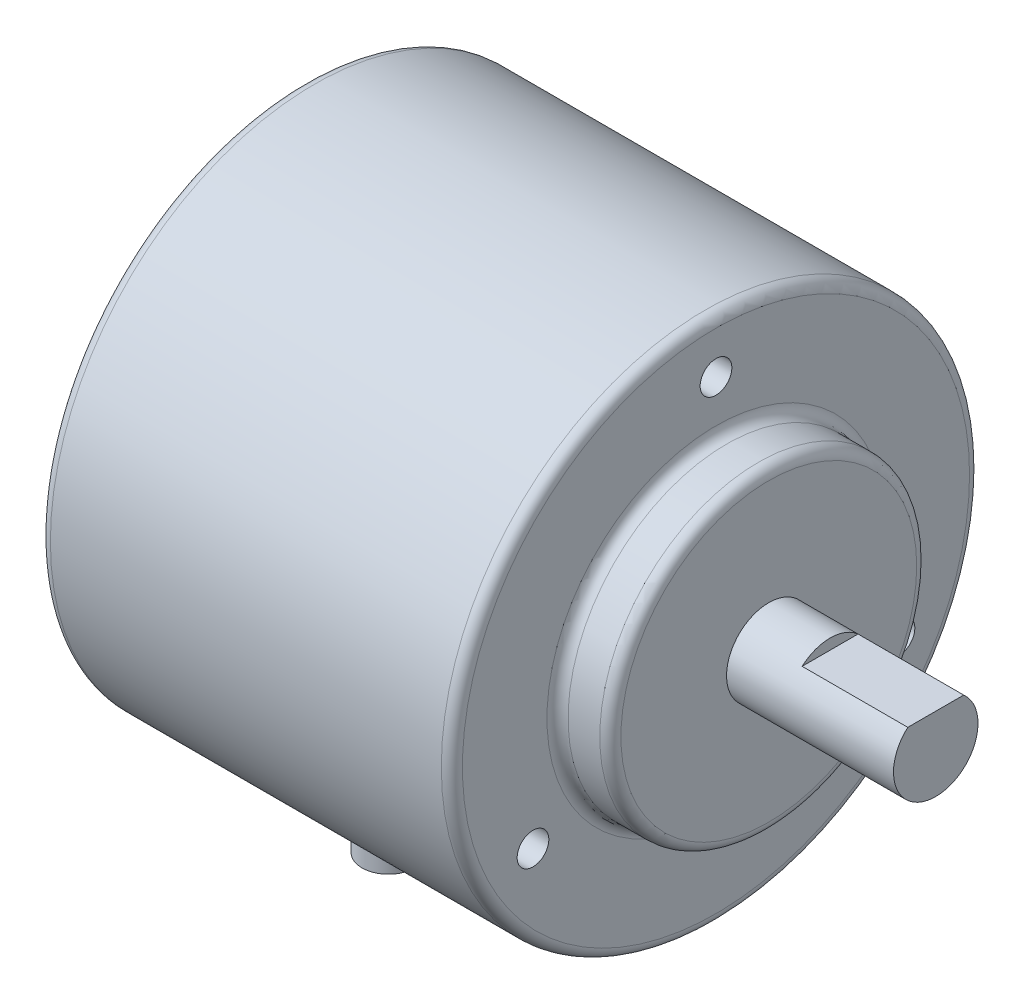
SolidWorks part; units mm, degrees
ref_plane "Front Plane" through (0, 0, 0) normal (0, 0, 1) x (1, 0, 0)
ref_plane "Top Plane" through (0, 0, 0) normal (0, 1, 0) x (1, 0, 0)
ref_plane "Right Plane" through (0, 0, 0) normal (1, 0, 0) x (0, 0, -1)
sketch "Sketch2" plane through (0, 0, 0) normal (1, 0, 0) x (0, 0, -1)
  circle A0 centre (0, 0) radius 25
  dimension "D1" = 50
extrude "Boss-Extrude1" add sketch "Sketch2" along normal blind 39
sketch "Sketch3" plane through (39, 0, 0) normal (1, 0, 0) x (0, 0, -1)
  circle A0 centre (0, 0) radius 15
  dimension "D1" = 30
extrude "Boss-Extrude2" add sketch "Sketch3" along normal blind 5
sketch "Sketch4" plane through (44, 0, 0) normal (1, 0, 0) x (0, 0, -1)
  circle A0 centre (0, 0) radius 4
  dimension "D1" = 8
extrude "Boss-Extrude3" add sketch "Sketch4" along normal blind 15.8
sketch "Sketch5" plane through (59.8, 0, 0) normal (1, 0, 0) x (0, 0, -1)
  line L0 (-3, 0) -> (3, 0) construction
  line L1 (-2.6458, 3) -> (2.6458, 3)
  line L2 (-3, 3) -> (3, 3) construction
  arc A1 (2.6458, 3) -> (-2.6458, 3) centre (0, 0) ccw
  dimension "D2" = 4
  dimension "D1" = 3
extrude "Cut-Extrude1" cut sketch "Sketch5" against normal blind 10
sketch "Sketch6" plane through (39, 0, 0) normal (1, 0, 0) x (0, 0, -1)
  circle A0 centre (0, 0) radius 20 construction
  circle A1 centre (0, 20) radius 1.5
  circle A2 centre (17.3205, -10) radius 1.5
  circle A3 centre (-17.3205, -10) radius 1.5
  point P12 (0, 0)
  dimension "D1" = 40
  dimension "D2" = 3
  dimension "D3" = 3
extrude "Cut-Extrude2" cut sketch "Sketch6" against normal blind 7
sketch3d "3DSketch1" plane through (0, 0, 0) normal (0, 0, 1) x (1, 0, 0)
  dimension "D1" = 20
sketch "Sketch8" plane through (0, -20, 0) normal (0, 1, 0) x (1, 0, 0)
  line L0 (0, 0) -> (39, 0) construction
  line L1 (39, -15) -> (39, 15) construction
  line L2 (0, 25) -> (0, -25) construction
  circle A0 centre (8, 0) radius 4
  dimension "D2" = 8
  dimension "D1" = 8
extrude "Boss-Extrude4" add sketch "Sketch8" along normal up to surface and the other way blind 7.5 up to face at (39, 0, -25)
sketch "Sketch9" plane through (0, -27.5, 0) normal (0, -1, 0) x (1, 0, 0)
  circle A0 centre (8, 0) radius 2.5
  dimension "D1" = 5
extrude "Boss-Extrude5" add sketch "Sketch9" along normal blind 7
fillet "Fillet1" radius 1 6 edges at (0, 0, -25) (39, 0, -25) (7.1371, -24.693, -3.9058) (8, -27.5, 2.5) (39, 0, -15) (44, 0, -15)
